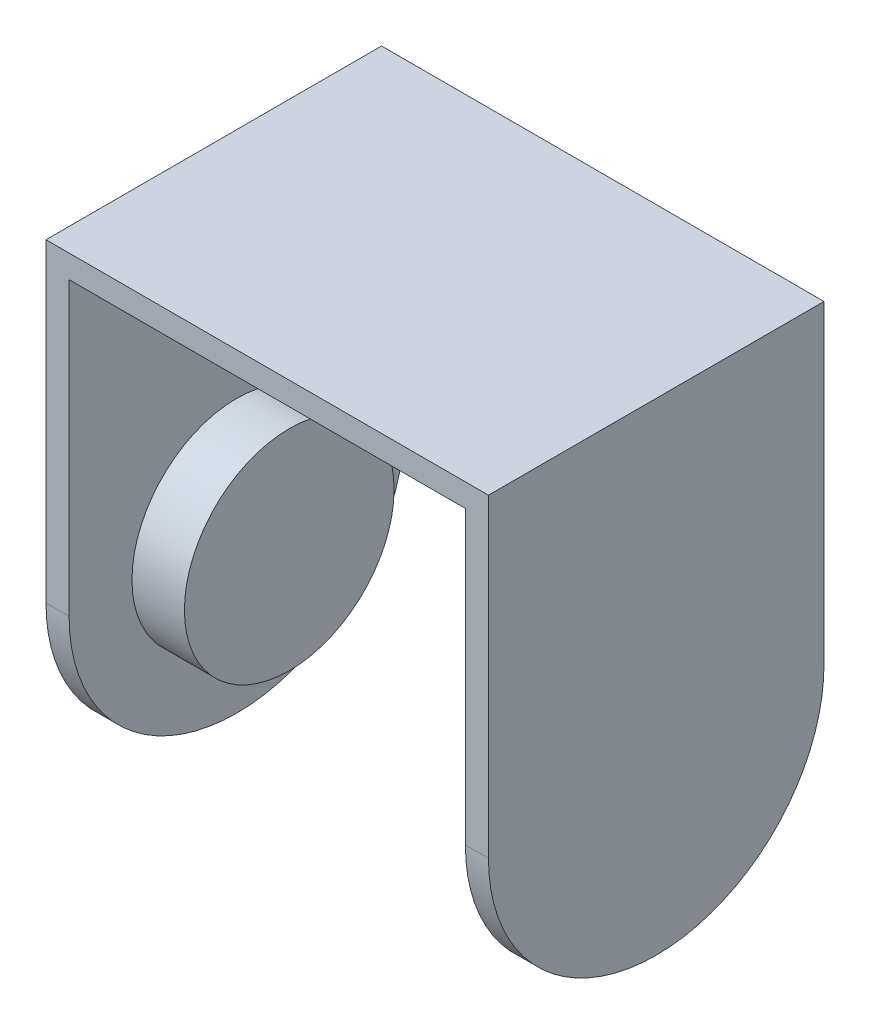
SolidWorks part; units mm, degrees
ref_plane "Front Plane" through (0, 0, 0) normal (0, 0, 1) x (1, 0, 0)
ref_plane "Top Plane" through (0, 0, 0) normal (0, 1, 0) x (1, 0, 0)
ref_plane "Right Plane" through (0, 0, 0) normal (1, 0, 0) x (0, 0, -1)
sketch "Sketch1" plane through (0, 0, 0) normal (0, 0, 1) x (1, 0, 0)
  line L0 (0, 0) -> (0, 46)
  line L1 (0, 46) -> (42.2, 46)
  line L2 (42.2, 46) -> (42.2, 0)
  line L3 (42.2, 0) -> (40, 0)
  line L4 (40, 0) -> (40, 43.8)
  line L5 (40, 43.8) -> (2.2, 43.8)
  line L6 (2.2, 43.8) -> (2.2, 0)
  line L7 (2.2, 0) -> (0, 0)
  dimension "D1" = 46
  dimension "D2" = 42.2
  dimension "D3" = 2.2
  dimension "D4" = 2.2
  dimension "D5" = 2.2
extrude "Boss-Extrude1" add sketch "Sketch1" along normal blind 32
fillet "Fillet1" radius 16 4 edges at (41.1, 0, 32) (41.1, 0, 0) (1.1, 0, 0) (1.1, 0, 32)
sketch "Sketch4" plane through (2.2, 0, 0) normal (1, 0, 0) x (0, 0, -1)
  circle A0 centre (-16, 16) radius 16
  circle A1 centre (-16, 16) radius 10
extrude "Boss-Extrude4" add sketch "Sketch4" along normal blind 5 contours A1
ref_plane "Plane1" through (21.1, 0, 0) normal (1, 0, 0) x (0, 0, -1)
mirror "Mirror1" about plane through (21.1, 0, 0) normal (1, 0, 0) of "Boss-Extrude4"
